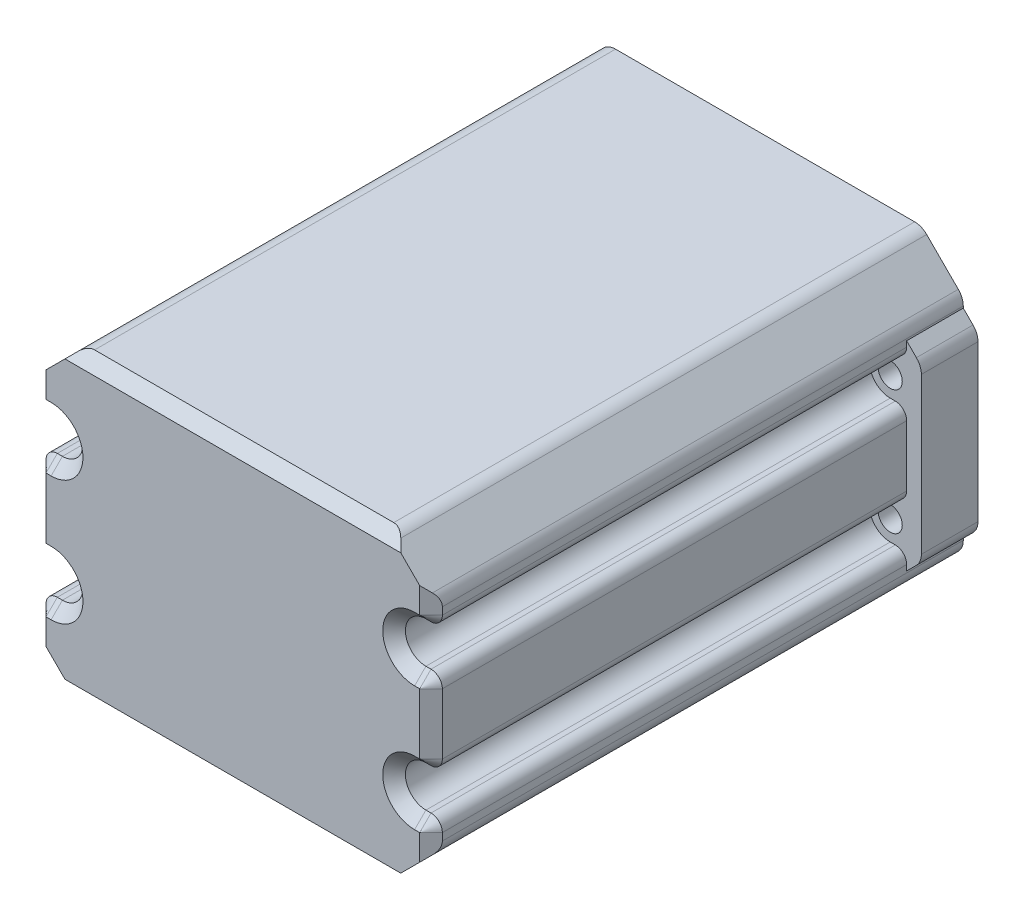
SolidWorks part; units mm, degrees
note: The reader was unsure of these and kept them because the rebuilt part matched: shared geometry of "Sketch1<3>".
ref_plane "Front Plane" through (0, 0, 0) normal (0, 0, 1) x (1, 0, 0)
ref_plane "Top Plane" through (0, 0, 0) normal (0, 1, 0) x (1, 0, 0)
ref_plane "Right Plane" through (0, 0, 0) normal (1, 0, 0) x (0, 0, -1)
sketch "Sketch1" plane through (0, 0, 0) normal (0, 0, 1) x (1, 0, 0)
  line L0 (27.6569, 53) -> (27.6569, 0) construction
  line L2 (-3.3431, 9.6017) -> (-3.3431, 9)
  line L4 (-4.4431, 41.125) -> (-7.3431, 41.125)
  line L5 (-4.4431, 33.875) -> (-7.3431, 33.875)
  line L6 (-4.4431, 11.875) -> (-7.3431, 11.875)
  line L7 (-4.4431, 19.125) -> (-7.3431, 19.125)
  line L8 (-7.3431, 41.5) -> (-9.9431, 41.5)
  line L13 (-9.9431, 41.5) -> (-9.9431, 11.5)
  line L17 (55.3137, 53) -> (0, 53)
  line L18 (0, 53) -> (-7.3431, 45.6569)
  line L19 (-7.3431, 45.6569) -> (-7.3431, 41.125)
  line L20 (-7.3431, 7.3431) -> (0, 0)
  line L21 (0, 0) -> (55.3137, 0)
  line L28 (-7.3431, 11.875) -> (-7.3431, 7.3431)
  line L29 (-7.3431, 33.875) -> (-7.3431, 19.125)
  line L30 (-7.3431, 33.875) -> (-7.3431, 19.125)
  line L33 (27.6569, 49) -> (1.6569, 49)
  line L37 (1.6569, 4) -> (27.6569, 4)
  line L38 (-3.3431, 9) -> (1.6569, 4)
  line L44 (1.5569, 37.5) -> (1.5569, 15.5)
  line L46 (1.6569, 49) -> (-3.3431, 44)
  line L47 (-3.3431, 44) -> (-3.3431, 43.3983)
  line L50 (-9.9431, 11.5) -> (-7.3431, 11.5)
  line L57 (65.2569, 11.5) -> (62.6569, 11.5)
  line L58 (58.6569, 44) -> (58.6569, 43.3983)
  line L59 (53.6569, 49) -> (58.6569, 44)
  line L60 (53.7569, 37.5) -> (53.7569, 15.5)
  line L61 (58.6569, 9) -> (53.6569, 4)
  line L62 (53.6569, 4) -> (27.6569, 4)
  line L63 (27.6569, 49) -> (53.6569, 49)
  line L64 (62.6569, 33.875) -> (62.6569, 19.125)
  line L66 (62.6569, 33.875) -> (62.6569, 19.125)
  line L67 (62.6569, 11.875) -> (62.6569, 7.3431)
  line L68 (62.6569, 7.3431) -> (55.3137, 0)
  line L70 (62.6569, 45.6569) -> (62.6569, 41.125)
  line L71 (55.3137, 53) -> (62.6569, 45.6569)
  line L72 (65.2569, 41.5) -> (65.2569, 11.5)
  line L73 (62.6569, 41.5) -> (65.2569, 41.5)
  line L74 (59.7569, 19.125) -> (62.6569, 19.125)
  line L75 (59.7569, 11.875) -> (62.6569, 11.875)
  line L76 (59.7569, 33.875) -> (62.6569, 33.875)
  line L77 (59.7569, 41.125) -> (62.6569, 41.125)
  line L78 (58.6569, 9.6017) -> (58.6569, 9)
  line L79 (-9.9431, 41.5) -> (-9.9431, 11.5) construction
  line L80 (-9.9431, 41.5) -> (-7.3431, 44.1)
  line L81 (-9.9431, 11.5) -> (-7.3431, 8.9)
  line L82 (-7.3431, 8.9) -> (-7.3431, 11.5)
  line L83 (-7.3431, 44.1) -> (-7.3431, 41.5)
  line L84 (62.6569, 41.5) -> (65.2569, 41.5)
  line L85 (65.2569, 41.5) -> (62.6569, 44.1)
  line L86 (65.2569, 41.5) -> (62.6569, 44.1) construction
  line L87 (62.6569, 44.1) -> (62.6569, 41.5)
  line L88 (65.2569, 11.5) -> (62.6569, 8.9)
  line L89 (62.6569, 8.9) -> (65.2569, 11.5) construction
  line L90 (62.6569, 8.9) -> (62.6569, 11.5)
  arc A0 (-4.4431, 33.875) -> (-4.4431, 41.125) centre (-4.4431, 37.5) ccw
  circle A1 centre (-4.4431, 15.5) radius 2.125
  circle A4 centre (-4.4431, 37.5) radius 2.125
  arc A5 (-4.4431, 11.875) -> (-4.4431, 19.125) centre (-4.4431, 15.5) ccw
  arc A14 (58.6569, 9.6017) -> (53.7569, 15.5) centre (59.7569, 15.5) cw
  arc A26 (1.5569, 37.5) -> (-3.3431, 43.3983) centre (-4.4431, 37.5) ccw
  arc A27 (-3.3431, 9.6017) -> (1.5569, 15.5) centre (-4.4431, 15.5) ccw
  arc A28 (53.7569, 37.5) -> (58.6569, 43.3983) centre (59.7569, 37.5) cw
  arc A29 (59.7569, 11.875) -> (59.7569, 19.125) centre (59.7569, 15.5) cw
  circle A30 centre (59.7569, 37.5) radius 2.125
  circle A31 centre (59.7569, 15.5) radius 2.125
  arc A32 (59.7569, 33.875) -> (59.7569, 41.125) centre (59.7569, 37.5) cw
  point P43 (14.6569, 4)
  point P44 (14.6569, 49)
  point P63 (40.6569, 49)
  point P64 (40.6569, 4)
  point P75 (1.5569, 26.5)
  point P76 (27.6569, 26.5)
  dimension "D3" = 7.25
  dimension "D4" = 4.25
  dimension "D5" = 12
  dimension "D6" = 22
  dimension "D7" = 32.1
  dimension "D1" = 45
  dimension "D2" = 45
  dimension "D8" = 4
  dimension "D9" = 45
  dimension "D10" = 5
  dimension "D11" = 4
  dimension "D12" = 4
  dimension "D13" = 4
  dimension "D14" = 5
  dimension "D15" = 4
  dimension "D16" = 31
extrude "Boss-Extrude1" add sketch "Sketch1" along normal blind 90
extrude "Boss-Extrude2" add sketch "Sketch1<3>" along normal blind 10
sketch "Sketch1<3>" plane through (0, 0, 0) normal (0, 0, 1) x (1, 0, 0) same geometry as "Sketch1"
fillet "Fillet1" radius 2 8 edges at (-7.3431, 41.125, 50) (-7.3431, 19.125, 50) (-7.3431, 11.875, 50) (-7.3431, 33.875, 50) (62.6569, 41.125, 50) (62.6569, 33.875, 50) (62.6569, 19.125, 50) (62.6569, 11.875, 50)
sketch "Sketch2" plane through (0, 0, 90) normal (0, 0, 1) x (1, 0, 0)
  line L21 (-7.3431, 31.875) -> (-7.3431, 21.125)
  line L28 (-7.3431, 9.875) -> (-7.3431, 7.3431)
  line L37 (55.3137, 0) -> (62.6569, 7.3431)
  line L43 (55.3137, 53) -> (0, 53)
  line L44 (0, 53) -> (-7.3431, 45.6569)
  line L45 (-7.3431, 45.6569) -> (-7.3431, 43.125)
  line L46 (-5.3431, 41.125) -> (-4.4431, 41.125)
  line L47 (-4.4431, 33.875) -> (-5.3431, 33.875)
  line L49 (-5.3431, 19.125) -> (-4.4431, 19.125)
  line L50 (-4.4431, 11.875) -> (-5.3431, 11.875)
  line L52 (-7.3431, 7.3431) -> (0, 0)
  line L53 (0, 0) -> (55.3137, 0)
  line L72 (62.6569, 7.3431) -> (62.6569, 9.875)
  line L82 (60.6569, 11.875) -> (59.7569, 11.875)
  line L86 (59.7569, 19.125) -> (60.6569, 19.125)
  line L90 (62.6569, 21.125) -> (62.6569, 31.875)
  line L92 (60.6569, 33.875) -> (59.7569, 33.875)
  line L94 (59.7569, 41.125) -> (60.6569, 41.125)
  line L96 (62.6569, 43.125) -> (62.6569, 45.6569)
  line L98 (62.6569, 45.6569) -> (55.3137, 53)
  arc A12 (59.7569, 19.125) -> (59.7569, 11.875) centre (59.7569, 15.5) ccw
  arc A15 (59.7569, 41.125) -> (59.7569, 33.875) centre (59.7569, 37.5) ccw
  arc A18 (-7.3431, 43.125) -> (-5.3431, 41.125) centre (-5.3431, 43.125) ccw
  arc A23 (-5.3431, 33.875) -> (-7.3431, 31.875) centre (-5.3431, 31.875) ccw
  arc A31 (-7.3431, 21.125) -> (-5.3431, 19.125) centre (-5.3431, 21.125) ccw
  arc A35 (-5.3431, 11.875) -> (-7.3431, 9.875) centre (-5.3431, 9.875) ccw
  arc A46 (-4.4431, 33.875) -> (-4.4431, 41.125) centre (-4.4431, 37.5) ccw
  arc A49 (-4.4431, 11.875) -> (-4.4431, 19.125) centre (-4.4431, 15.5) ccw
  arc A62 (60.6569, 41.125) -> (62.6569, 43.125) centre (60.6569, 43.125) ccw
  arc A64 (62.6569, 9.875) -> (60.6569, 11.875) centre (60.6569, 9.875) ccw
  arc A66 (60.6569, 19.125) -> (62.6569, 21.125) centre (60.6569, 21.125) ccw
  arc A68 (62.6569, 31.875) -> (60.6569, 33.875) centre (60.6569, 31.875) ccw
extrude "Boss-Extrude3" add sketch "Sketch2" along normal blind 4
chamfer "Chamfer1" distance 2 angle 45 28 edges at (27.6569, 0, 94) (27.6569, 53, 94) (-4.8931, 11.875, 94) (-0.8181, 15.5, 94) (-4.8931, 19.125, 94) (-7.3431, 44.3909, 94) (-7.3431, 26.5, 94) (-7.3431, 8.6091, 94) (-6.7574, 41.7108, 94) (-4.8931, 41.125, 94) (-4.8931, 33.875, 94) (-0.8181, 37.5, 94) (-6.7574, 11.2892, 94) (-6.7574, 19.7108, 94) (-6.7574, 33.2892, 94) (62.6569, 8.6091, 94) (62.6569, 44.3909, 94) (62.0711, 11.2892, 94) (62.0711, 41.7108, 94) (60.2069, 11.875, 94) (60.2069, 41.125, 94) (56.1319, 15.5, 94) (56.1319, 37.5, 94) (60.2069, 19.125, 94) (60.2069, 33.875, 94) (62.0711, 19.7108, 94) (62.0711, 33.2892, 94) (62.6569, 26.5, 94)
fillet "Fillet3" radius 3 12 edges at (-9.9431, 11.5, 5) (65.2569, 11.5, 5) (65.2569, 41.5, 5) (62.6569, 45.6569, 46) (55.3137, 53, 46) (0, 53, 46) (-7.3431, 45.6569, 46) (-9.9431, 41.5, 5) (55.3137, 0, 46) (62.6569, 7.3431, 46) (0, 0, 46) (-7.3431, 7.3431, 46)
